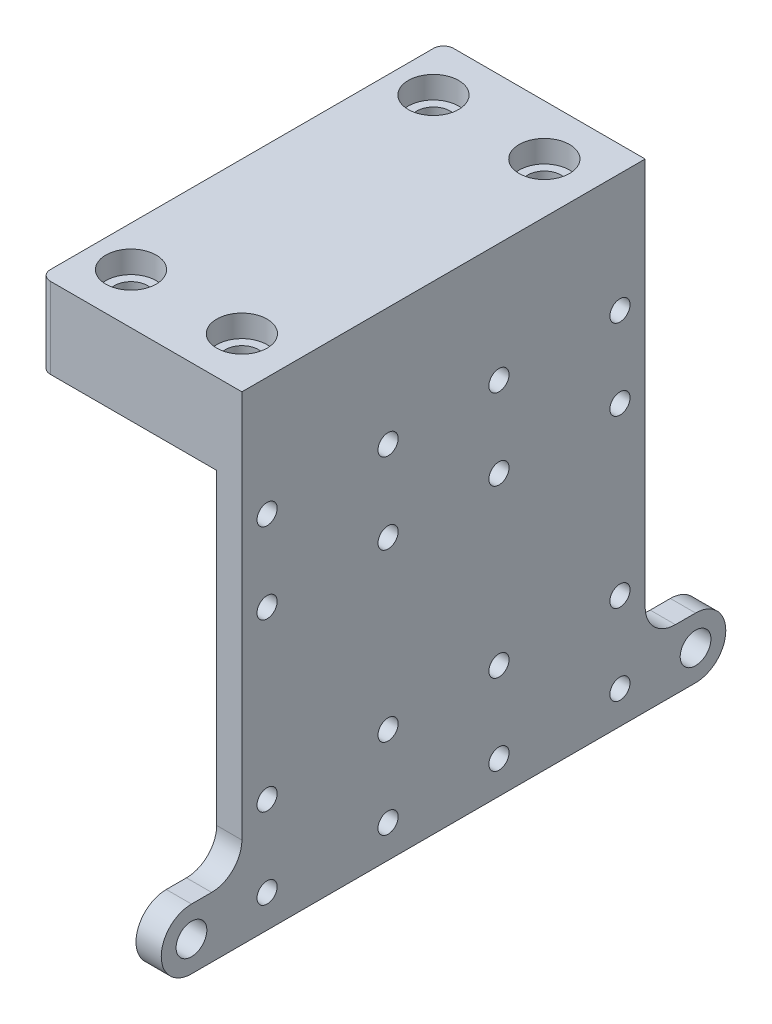
SolidWorks part; units mm, degrees
note: '?' marks a value the reader was unsure of.
material "6061 合金"
ref_plane "前视基准面" through (0, 0, 0) normal (0, 0, 1) x (1, 0, 0)
ref_plane "上视基准面" through (0, 0, 0) normal (0, 1, 0) x (1, 0, 0)
ref_plane "右视基准面" through (0, 0, 0) normal (1, 0, 0) x (0, 0, -1)
other "Configuration Table"
sketch "草图1" plane through (0, 0, 0) normal (0, 0, 1) x (1, 0, 0)
  line L0 (0, 0) -> (20, 0)
  line L1 (20, 0) -> (20, -47.5)
  line L2 (20, -47.5) -> (17.5, -47.5)
  line L3 (17.5, -47.5) -> (17.5, -8)
  line L6 (17.5, -8) -> (0, -8)
  line L7 (0, -8) -> (0, 0)
  dimension "D1" = 8
  dimension "D2" = 2.5
  dimension "D3" = 47.5
  dimension "D4" = 20
extrude "凸台-拉伸1" add sketch "草图1" along normal mid plane 40
sketch "草图2" plane through (0, 0, 0) normal (0, 0, 1) x (1, 0, 0)
  line L0 (0, -8) -> (17.5, -47.5)
rib "筋1" sketch "草图2" sketch "草图2" thickness 4 extrusion direction parallel to sketch draft on no parameters "D1"=4
sketch "草图3" plane through (0, -8, 0) normal (0, -1, 0) x (1, 0, 0)
  line L0 (8.75, -2) -> (8.75, -20) construction
  line L3 (0, -2) -> (17.5, -2) construction
  line L4 (0, -20) -> (17.5, -20) construction
  line L5 (4, -15) -> (15, -15) construction
  line L6 (0, -2) -> (0, -20) construction
  line L7 (17.5, -2) -> (17.5, -20) construction
  line L8 (4, -15) -> (8.75, -15) construction
  point P9 (8.75, -11)
  dimension "D1" = 4
  dimension "D2" = 2.5
  dimension "D3" = 5
hole_wizard "M4 螺纹孔1" positions "草图4" profile "草图5" tap size "M4" standard "GB" end condition through all
sketch "草图4" plane through (0, -8, 0) normal (0, -1, 0) x (-1, 0, 0)
  point P0 (-4, 15)
  point P3 (-15, 15)
sketch "草图5" plane through (4, -8, -15) normal (1, 0, 0) x (0, 0, -1)
  line L0 (0, 0) -> (0, 8)
  line L1 (0, 8) -> (1.65, 8)
  line L2 (1.65, 8) -> (1.65, 0)
  line L5 (1.65, 0) -> (0, 0)
  line L11 (0, -6.35) -> (0, 107.95) construction
  dimension "通孔螺纹孔钻头直径" = 3.3
  dimension "通孔螺纹孔钻头深度" = 8
cosmetic thread "孔螺蚊线1" parameters "D2"=4
cosmetic thread "孔螺蚊线2" parameters "D2"=4
mirror "镜向1" about plane through (0, 0, 0) normal (0, 0, 1) of "M4 螺纹孔1"
sketch "草图6" plane through (0, 0, 0) normal (0, 1, 0) x (1, 0, 0)
  circle A0 centre (15, 15) radius 2.5
  circle A1 centre (4, 15) radius 2.5
  circle A2 centre (4, -15) radius 2.5
  circle A3 centre (15, -15) radius 2.5
  dimension "D1" = 5
extrude "切除-拉伸1" cut sketch "草图6" against normal blind 2.2
sketch "草图7" plane through (17.5, 0, 0) normal (-1, 0, 0) x (0, 0, 1)
  line L0 (0, 0) -> (0, -51.3237) construction
  circle A0 centre (-5.5, -44.25) radius 1 construction
  circle A1 centre (-17.5, -44.25) radius 1 construction
  circle A2 centre (-5.5, -36.25) radius 1 construction
  circle A3 centre (-17.5, -36.25) radius 1 construction
  circle A4 centre (-5.5, -19.75) radius 1 construction
  circle A5 centre (-5.5, -11.75) radius 1 construction
  circle A6 centre (-17.5, -19.75) radius 1 construction
  circle A7 centre (-17.5, -11.75) radius 1 construction
  circle A8 centre (-5.5, -44.25) radius 1
  circle A9 centre (-17.5, -44.25) radius 1
  circle A10 centre (-5.5, -36.25) radius 1
  circle A11 centre (-17.5, -36.25) radius 1
  circle A12 centre (-5.5, -19.75) radius 1
  circle A13 centre (-5.5, -11.75) radius 1
  circle A14 centre (-17.5, -19.75) radius 1
  circle A15 centre (-17.5, -11.75) radius 1
  circle A16 centre (17.5, -11.75) radius 1
  circle A17 centre (17.5, -19.75) radius 1
  circle A18 centre (5.5, -11.75) radius 1
  circle A19 centre (5.5, -19.75) radius 1
  circle A20 centre (17.5, -36.25) radius 1
  circle A21 centre (5.5, -36.25) radius 1
  circle A22 centre (17.5, -44.25) radius 1
  circle A23 centre (5.5, -44.25) radius 1
extrude "切除-拉伸2" cut sketch "草图7" against normal blind 10
fillet "圆角1" radius 1 4 edges at (18.75, -47.5, 20) (18.75, -47.5, -20) (0, -4, 20) (0, -4, -20)
sketch "草图8" plane through (17.5, 0, 0) normal (-1, 0, 0) x (0, 0, 1)
  line L0 (19, -47.5) -> (2, -47.5) construction
  line L1 (20, -8) -> (20, -46.5) construction
  line L2 (19, -47.5) -> (25, -47.5)
  line L3 (25, -41.5) -> (20, -41.5)
  line L4 (20, -41.5) -> (19, -47.5)
  circle A0 centre (25, -44.5) radius 1.525
  arc A1 (25, -47.5) -> (25, -41.5) centre (25, -44.5) ccw
  dimension "D1" = 3.05
  dimension "D2" = 3
  dimension "D3" = 5
extrude "凸台-拉伸2" add sketch "草图8" against normal up to surface (2.5 mm away) up to face at (20, -12.75, -5.5)
mirror "镜向2" about plane through (0, 0, 0) normal (0, 0, 1) of "凸台-拉伸2"
fillet "圆角2" radius 3 2 edges at (18.75, -41.5, -20) (18.75, -41.5, 20)
sketch "草图9" plane through (0, 0, 2) normal (0, 0, 1) x (1, 0, 0)
  line L0 (4.375, -8) -> (17.5, -37.625)
  line L1 (0, -8) -> (17.5, -8) construction
  line L2 (17.5, -8) -> (17.5, -38.5) construction
  line L3 (17.5, -37.625) -> (17.5, -8)
  line L4 (17.5, -8) -> (4.375, -8)
  line L5 (0, -8) -> (17.5, -47.5) construction
  dimension "D1" = 4
extrude "切除-拉伸3" [suppressed] cut sketch "草图9" against normal up to surface (4 mm away)
fillet "圆角3" [suppressed] radius 1.5?
sketch "草图10" plane through (17.5, 0, 0) normal (-1, 0, 0) x (0, 0, 1)
  line L0 (25, -47.5) -> (2, -47.5) construction
  line L1 (-20, -47.5) -> (20, -47.5)
  line L2 (-20, -47.5) -> (-20, -8)
  line L3 (-20, -8) -> (20, -8)
  line L4 (20, -47.5) -> (20, -8)
  line L5 (-20, -47.5) -> (20, -8) construction
  line L6 (-20, -8) -> (20, -47.5) construction
  line L7 (-2, -47.5) -> (-25, -47.5) construction
  line L8 (-20, -8) -> (-20, -38.5) construction
  point P0 (0, -27.75)
extrude "凸台-拉伸3" [suppressed] add sketch "草图10" against normal up to surface (2.5 mm away)
other "移动面1" [suppressed] parameters "D1"=15
sketch "草图11" [suppressed] plane through (17.5, 0, 0) normal (-1, 0, 0) x (0, 0, 1)
  line L0 (0, 0) -> (0, -45) construction
  line L1 (-5, -52.5) -> (5, -52.5) construction
  line L2 (-5, -52.5) -> (-5, -37.5) construction
  line L3 (-5, -37.5) -> (5, -37.5) construction
  line L4 (5, -52.5) -> (5, -37.5) construction
  line L5 (-5, -52.5) -> (5, -37.5) construction
  line L6 (-5, -37.5) -> (5, -52.5) construction
  line L8 (-5, -27.5) -> (5, -27.5) construction
  line L9 (-5, -27.5) -> (-5, -12.5) construction
  line L10 (-5, -12.5) -> (5, -12.5) construction
  line L11 (5, -27.5) -> (5, -12.5) construction
  line L12 (-5, -27.5) -> (5, -12.5) construction
  line L13 (-5, -12.5) -> (5, -27.5) construction
  circle A0 centre (-5, -12.5) radius 1.51
  circle A1 centre (5, -12.5) radius 1.51
  circle A2 centre (5, -27.5) radius 1.51
  circle A3 centre (-5, -27.5) radius 1.51
  circle A4 centre (-5, -37.5) radius 1.51
  circle A5 centre (5, -37.5) radius 1.51
  circle A6 centre (5, -52.5) radius 1.51
  circle A7 centre (-5, -52.5) radius 1.51
  point P0 (0, -45)
  point P10 (0, -20)
  dimension "D7" = 3.02
  dimension "D1" = 15
  dimension "D2" = 10
  dimension "D3" = 15
  dimension "D4" = 10
  dimension "D5" = 20
  dimension "D6" = 25
